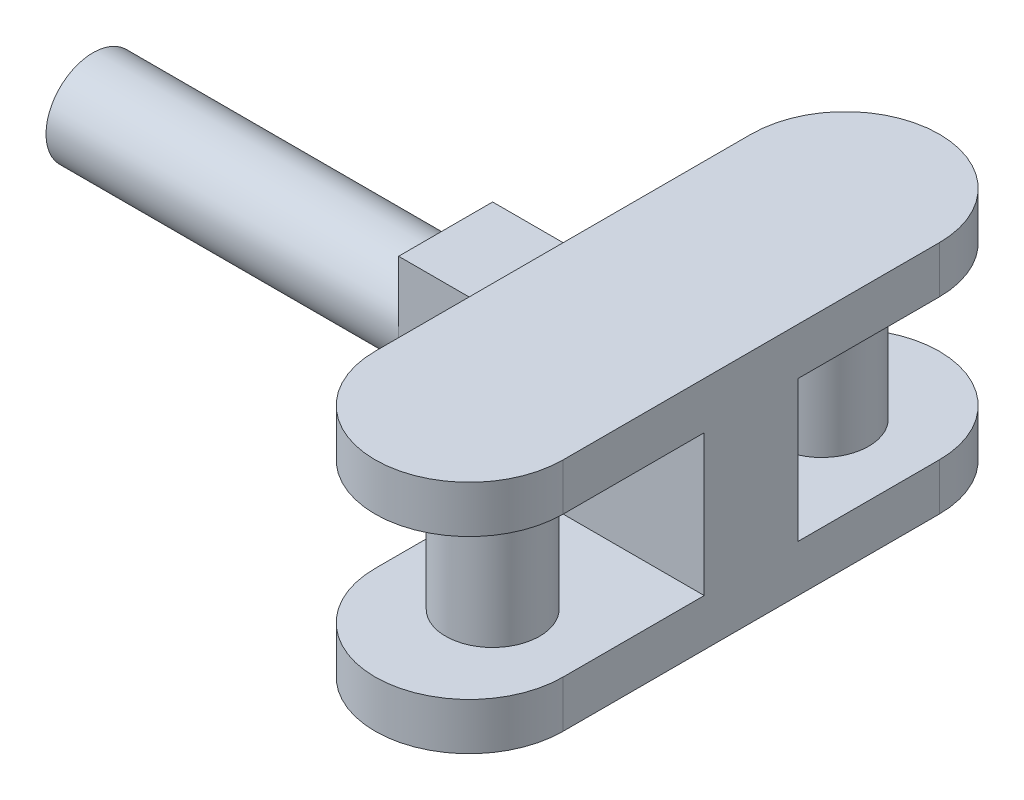
SolidWorks part; units mm, degrees
ref_plane "Plan de face" through (0, 0, 0) normal (0, 0, 1) x (1, 0, 0)
ref_plane "Plan de dessus" through (0, 0, 0) normal (0, 1, 0) x (1, 0, 0)
ref_plane "Plan de droite" through (0, 0, 0) normal (1, 0, 0) x (0, 0, -1)
sketch "Esquisse1" plane through (0, 0, 0) normal (0, 1, 0) x (1, 0, 0)
  line L1 (0, 0) -> (8, 0)
  line L2 (0, 0) -> (0, 24)
  line L3 (0, 24) -> (8, 24)
  line L4 (8, 0) -> (8, 24)
  dimension "D1" = 24
  dimension "D2" = 8
extrude "Boss.-Extru.1" add sketch "Esquisse1" along normal blind 10
sketch "Esquisse2" plane through (8, 0, 0) normal (1, 0, 0) x (0, 0, -1)
  line L0 (0, 10) -> (0, 0) construction
  line L1 (0, 8) -> (10, 8)
  line L2 (0, 8) -> (0, 2)
  line L3 (0, 2) -> (10, 2)
  line L4 (10, 8) -> (10, 2)
  line L5 (24, 10) -> (24, 0) construction
  line L6 (24, 8) -> (14, 8)
  line L7 (24, 8) -> (24, 2)
  line L8 (24, 2) -> (14, 2)
  line L9 (14, 8) -> (14, 2)
  line L10 (0, 0) -> (24, 0) construction
  dimension "D1" = 6
  dimension "D2" = 2
  dimension "D3" = 2
  dimension "D4" = 6
  dimension "D5" = 10
  dimension "D6" = 10
extrude "Enlèv. mat.-Extru.1" cut sketch "Esquisse2" against normal blind 10
sketch "Esquisse3" plane through (0, 2, 0) normal (0, 1, 0) x (1, 0, 0)
  line L0 (0, 0) -> (8, 0) construction
  line L1 (0, 24) -> (8, 24) construction
  line L2 (8, 0) -> (8, 10) construction
  line L3 (8, 14) -> (8, 24) construction
  circle A0 centre (4, 5) radius 2
  circle A1 centre (4, 19) radius 2
  dimension "D1" = 4
  dimension "D2" = 4
  dimension "D3" = 5
  dimension "D4" = 5
  dimension "D5" = 4
  dimension "D6" = 4
extrude "Boss.-Extru.2" add sketch "Esquisse3" along normal blind 6
fillet "Congé1" 2 edges at (0, 1, -24) (8, 1, -24) type full round first side face at (0, 5, -12) second side face at (8, 5, -12) middle face at (4, 1, -24)
fillet "Congé2" 2 edges at (0, 9, -24) (8, 9, -24) type full round first side face at (0, 5, -11.3333) second side face at (8, 5, -11.3333) middle face at (4, 9, -24)
fillet "Congé3" 2 edges at (0, 9, 0) (8, 9, 0) type full round first side face at (0, 5, -10.6667) second side face at (8, 5, -10.6667) middle face at (4, 9, 0)
fillet "Congé4" 2 edges at (0, 1, 0) (8, 1, 0) type full round first side face at (0, 5, -11.3333) second side face at (8, 5, -11.3333) middle face at (4, 1, 0)
sketch "Esquisse4" plane through (0, 0, 0) normal (-1, 0, 0) x (0, 0, 1)
  line L0 (-20, 10) -> (-4, 10) construction
  line L1 (-10, 2) -> (-10, 8) construction
  circle A0 centre (-12, 5) radius 2
  dimension "D2" = 4
  dimension "D1" = 5
  dimension "D3" = 2
extrude "Boss.-Extru.3" add sketch "Esquisse4" along normal blind 20
sketch "Esquisse5" plane through (0, 0, 0) normal (-1, 0, 0) x (0, 0, 1)
  line L1 (-14, 8) -> (-10, 8)
  line L2 (-14, 8) -> (-14, 2)
  line L3 (-14, 2) -> (-10, 2)
  line L4 (-10, 8) -> (-10, 2)
extrude "Boss.-Extru.4" add sketch "Esquisse5" along normal blind 5
